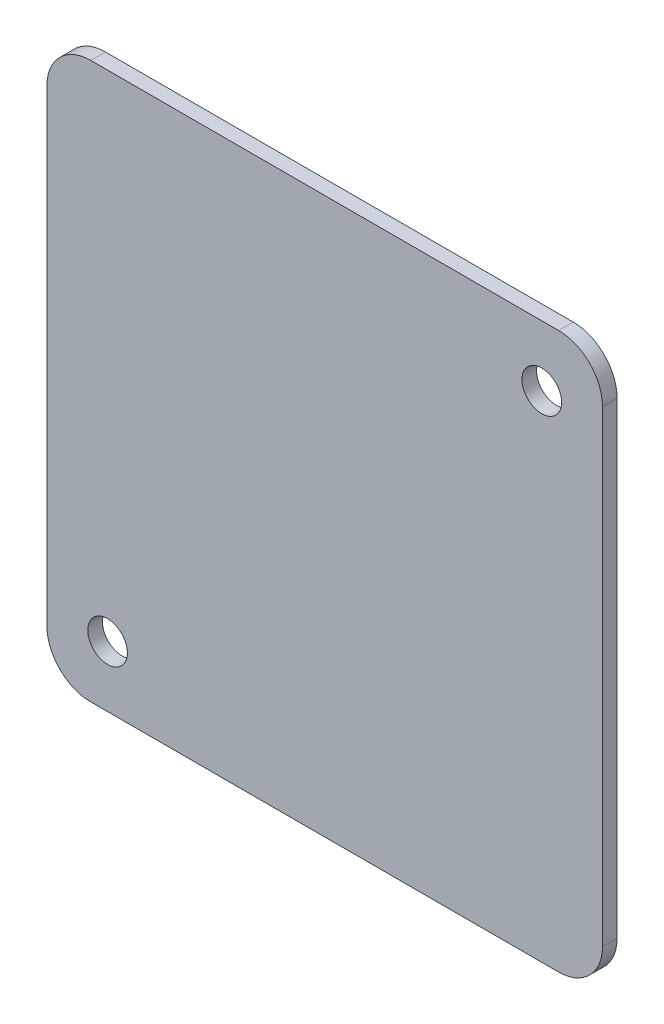
SolidWorks part; units mm, degrees
ref_plane "Front Plane" through (0, 0, 0) normal (0, 0, 1) x (1, 0, 0)
ref_plane "Top Plane" through (0, 0, 0) normal (0, 1, 0) x (1, 0, 0)
ref_plane "Right Plane" through (0, 0, 0) normal (1, 0, 0) x (0, 0, -1)
sketch "Sketch1" plane through (0, 0, 0) normal (0, 0, 1) x (1, 0, 0)
  line L8 (-23.8125, -87.0764) -> (-23.8125, -36.2764)
  line L9 (-28.575, -31.5139) -> (-79.375, -31.5139)
  line L10 (-84.1375, -36.2764) -> (-84.1375, -87.0764)
  line L11 (-79.375, -91.8389) -> (-28.575, -91.8389)
  line L12 (-23.8125, -87.0764) -> (-23.8125, -36.2764)
  line L13 (-28.575, -31.5139) -> (-79.375, -31.5139)
  line L14 (-84.1375, -36.2764) -> (-84.1375, -87.0764)
  line L15 (-79.375, -91.8389) -> (-28.575, -91.8389)
  arc A8 (-28.575, -91.8389) -> (-23.8125, -87.0764) centre (-28.575, -87.0764) ccw
  arc A9 (-23.8125, -36.2764) -> (-28.575, -31.5139) centre (-28.575, -36.2764) ccw
  arc A10 (-79.375, -31.5139) -> (-84.1375, -36.2764) centre (-79.375, -36.2764) ccw
  arc A11 (-84.1375, -87.0764) -> (-79.375, -91.8389) centre (-79.375, -87.0764) ccw
  arc A12 (-28.575, -91.8389) -> (-23.8125, -87.0764) centre (-28.575, -87.0764) ccw
  arc A13 (-23.8125, -36.2764) -> (-28.575, -31.5139) centre (-28.575, -36.2764) ccw
  arc A14 (-79.375, -31.5139) -> (-84.1375, -36.2764) centre (-79.375, -36.2764) ccw
  arc A15 (-84.1375, -87.0764) -> (-79.375, -91.8389) centre (-79.375, -87.0764) ccw
  dimension "D1" = 0
extrude "Boss-Extrude1" add sketch "Sketch1" against normal blind 1.5875
hole_wizard "#6 Clearance Hole1" positions "Sketch3" profile "Sketch2" hole size "#6" standard "ANSI Inch" end condition through all
sketch "Sketch3" plane through (0, 0, -1.5875) normal (0, 0, -1) x (-1, 0, 0)
  point P0 (30.4018, -38.1033)
  point P3 (77.5482, -85.2496)
sketch "Sketch2" plane through (-30.4018, -38.1033, -1.5875) normal (1, 0, 0) x (0, 1, 0)
  line L0 (0, 0) -> (0, 1.5875)
  line L1 (0, 1.5875) -> (2.1526, 1.5875)
  line L2 (2.1526, 1.5875) -> (2.1526, 0)
  line L5 (2.1526, 0) -> (0, 0)
  line L11 (0, -6.35) -> (0, 107.95) construction
  dimension "Thru Hole Dia." = 4.3053
  dimension "Thru Hole Depth" = 1.5875
